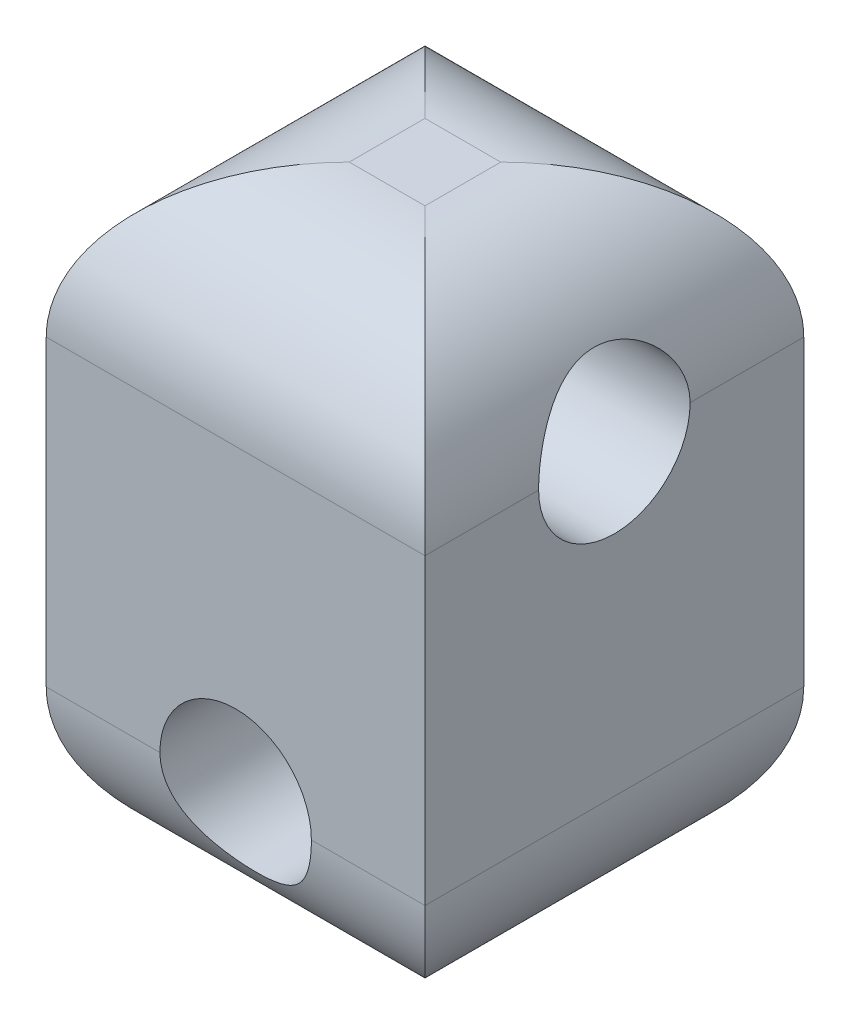
SolidWorks part; units mm, degrees
ref_plane "Alzado" through (0, 0, 0) normal (0, 0, 1) x (1, 0, 0)
ref_plane "Planta" through (0, 0, 0) normal (0, 1, 0) x (1, 0, 0)
ref_plane "Vista lateral" through (0, 0, 0) normal (1, 0, 0) x (0, 0, -1)
sketch "Croquis1" plane through (0, 0, 0) normal (0, 0, 1) x (1, 0, 0)
  line L1 (-3.3135, 5.7231) -> (-0.8135, 5.7231)
  line L2 (-3.3135, 5.7231) -> (-3.3135, 1.7231)
  line L3 (-3.3135, 1.7231) -> (-0.8135, 1.7231)
  line L4 (-0.8135, 5.7231) -> (-0.8135, 1.7231)
  dimension "D1" = 2.5
  dimension "D2" = 4
extrude "Saliente-Extruir1" add sketch "Croquis1" along normal blind 2.5
fillet "Redondeo1" radius 1 4 edges at (-3.3135, 1.7231, 1.25) (-0.8135, 1.7231, 1.25) (-2.0635, 5.7231, 0) (-2.0635, 5.7231, 2.5)
sketch "Croquis2" plane through (-0.8135, 0, 0) normal (1, 0, 0) x (0, 0, -1)
  line L0 (-2.5, 2.7231) -> (-2.5, 4.7231) construction
  line L1 (0, 2.7231) -> (0, 4.7231) construction
  line L2 (-1.5, 5.7231) -> (-1, 5.7231) construction
  circle A0 centre (-1.25, 4.7231) radius 0.5
  dimension "D1" = 1
  dimension "D2" = 1.25
  dimension "D3" = 1.25
  dimension "D4" = 1
extrude "Cortar-Extruir1" cut sketch "Croquis2" against normal blind 2.5
sketch "Croquis4" plane through (0, 0, 2.5) normal (0, 0, 1) x (1, 0, 0)
  line L0 (-0.8135, 2.7231) -> (-0.8135, 4.7231) construction
  line L1 (-2.3135, 1.7231) -> (-1.8135, 1.7231) construction
  circle A0 centre (-2.0635, 2.7231) radius 0.5
  dimension "D1" = 1
  dimension "D2" = 1.25
  dimension "D3" = 1
extrude "Cortar-Extruir2" cut sketch "Croquis4" against normal blind 2.5
fillet "Redondeo2" radius 1 2 edges at (-0.8135, 5.7231, 1.25) (-3.3135, 5.7231, 1.25)
fillet "Redondeo3" radius 1 2 edges at (-2.0635, 1.7231, 2.5) (-2.0635, 1.7231, 0)
